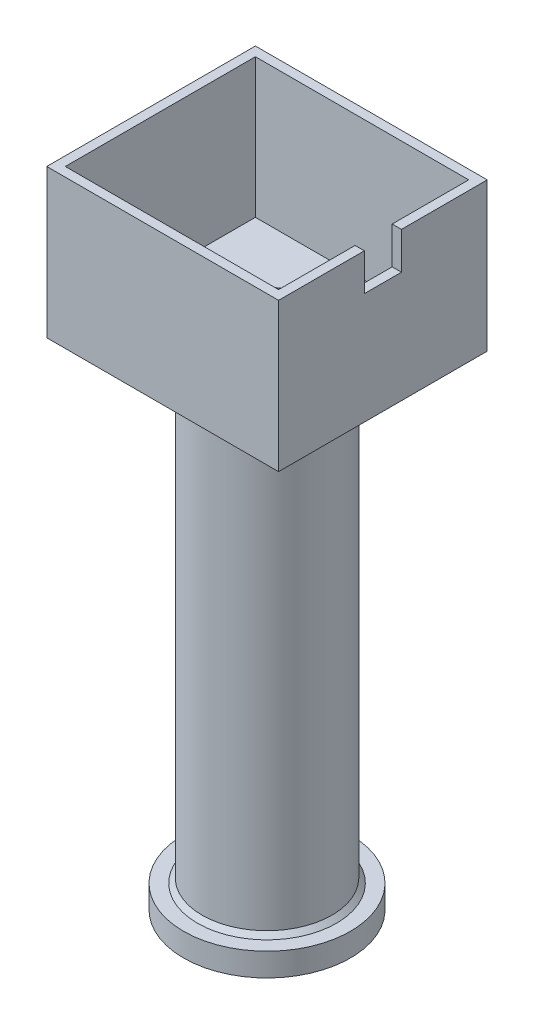
SolidWorks part; units mm, degrees
ref_plane "Front Plane" through (0, 0, 0) normal (0, 0, 1) x (1, 0, 0)
ref_plane "Top Plane" through (0, 0, 0) normal (0, 1, 0) x (1, 0, 0)
ref_plane "Right Plane" through (0, 0, 0) normal (1, 0, 0) x (0, 0, -1)
sketch "Sketch1" plane through (0, 0, 0) normal (0, 1, 0) x (1, 0, 0)
  line L7 (8.0829, -14) -> (16.1658, 0)
  line L8 (16.1658, 0) -> (8.0829, 14)
  line L9 (8.0829, 14) -> (-8.0829, 14)
  line L10 (-8.0829, 14) -> (-16.1658, 0)
  line L11 (-16.1658, 0) -> (-8.0829, -14)
  line L12 (-8.0829, -14) -> (8.0829, -14)
  circle A0 centre (0, 0) radius 14 construction
  circle A1 centre (0, 0) radius 18
  dimension "D2" = 36
  dimension "D1" = 28
extrude "Boss-Extrude1" add sketch "Sketch1" along normal blind 4
sketch "Sketch2" plane through (0, 4, 0) normal (0, 1, 0) x (1, 0, 0)
  circle A0 centre (0, 0) radius 12.25
  circle A1 centre (0, 0) radius 14
  dimension "D1" = 24.5
  dimension "D2" = 28
extrude "Boss-Extrude2" add sketch "Sketch2" along normal blind 101.6 separate body
sketch "Sketch3" plane through (0, 4, 0) normal (0, 1, 0) x (1, 0, 0)
  circle A0 centre (0, 0) radius 18 construction
  circle A1 centre (0, 0) radius 18
  circle A2 centre (0, 0) radius 12.25 construction
  circle A3 centre (0, 0) radius 12.25
extrude "Boss-Extrude3" add sketch "Sketch3" along normal blind 1
chamfer "Chamfer1" distance 1 angle 45 1 edges at (0, 5, 14)
sketch "Sketch4" plane through (0, 105.6, 0) normal (0, 1, 0) x (1, 0, 0)
  line L0 (0, 22.5) -> (0, -22.5) construction
  line L1 (-25, 22.5) -> (25, 22.5)
  line L2 (-25, 22.5) -> (-25, -22.5)
  line L3 (-25, -22.5) -> (25, -22.5)
  line L4 (25, 22.5) -> (25, -22.5)
  line L5 (-25, 0) -> (25, 0) construction
  circle A0 centre (0, 0) radius 12.25 construction
  circle A1 centre (0, 0) radius 12.25
  dimension "D1" = 45
  dimension "D2" = 50
extrude "Boss-Extrude4" add sketch "Sketch4" along normal blind 2
sketch "Sketch5" plane through (0, 107.6, 0) normal (0, 1, 0) x (1, 0, 0)
  line L0 (23, 20.5) -> (-23, 20.5)
  line L1 (-23, 20.5) -> (-23, -20.5)
  line L2 (-23, -20.5) -> (23, -20.5)
  line L3 (23, -20.5) -> (23, 20.5)
  line L4 (-25, 22.5) -> (-25, -22.5)
  line L5 (-25, -22.5) -> (25, -22.5)
  line L6 (25, -22.5) -> (25, 22.5)
  line L7 (25, 22.5) -> (-25, 22.5)
  line L8 (-25, 22.5) -> (-25, -22.5)
  line L9 (-25, -22.5) -> (25, -22.5)
  line L10 (25, -22.5) -> (25, 22.5)
  line L11 (25, 22.5) -> (-25, 22.5)
  dimension "D1" = 0
  dimension "D2" = 2
extrude "Boss-Extrude5" add sketch "Sketch5" along normal blind 30
chamfer "Chamfer2" distance 5 angle 45 1 edges at (0, 105.6, 14)
sketch "Sketch6" plane through (25, 0, 0) normal (1, 0, 0) x (0, 0, -1)
  line L0 (-22.5, 137.6) -> (22.5, 137.6) construction
  line L1 (-4, 137.6) -> (4, 137.6)
  line L2 (-4, 137.6) -> (-4, 129.6)
  line L3 (-4, 129.6) -> (4, 129.6)
  line L4 (4, 137.6) -> (4, 129.6)
  line L5 (0, 105.6) -> (0, 137.6) construction
  line L6 (-19, 105.6) -> (19, 105.6) construction
  dimension "D1" = 8
  dimension "D2" = 8
extrude "Cut-Extrude1" cut sketch "Sketch6" against normal blind 20
